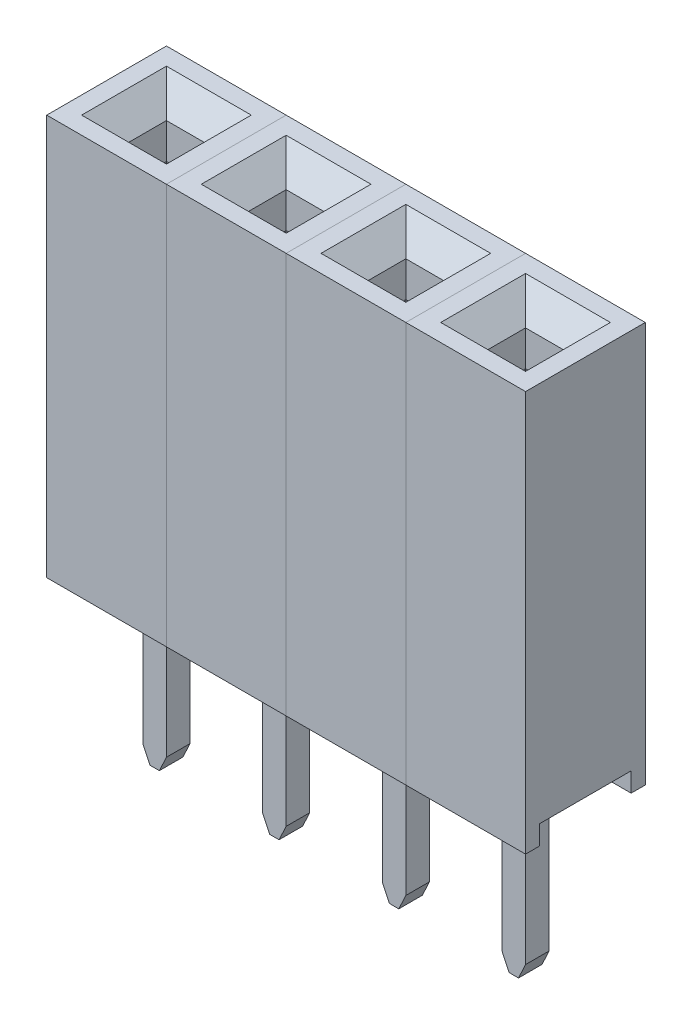
SolidWorks part; units mm, degrees
ref_plane "Front" through (0, 0, 0) normal (0, 0, 1) x (1, 0, 0)
ref_plane "Top" through (0, 0, 0) normal (0, 1, 0) x (1, 0, 0)
ref_plane "Right" through (0, 0, 0) normal (1, 0, 0) x (0, 0, -1)
sketch "Sketch1" plane through (0, 0, 0) normal (0, 0, 1) x (1, 0, 0)
  line L1 (1.27, -4.25) -> (-1.27, -4.25)
  line L2 (1.27, -4.25) -> (1.27, 4.25)
  line L3 (1.27, 4.25) -> (-1.27, 4.25)
  line L4 (-1.27, -4.25) -> (-1.27, 4.25)
  line L5 (1.27, -4.25) -> (-1.27, 4.25) construction
  line L6 (1.27, 4.25) -> (-1.27, -4.25) construction
  point P0 (0, 0)
  dimension "D1" = 2.54
  dimension "D2" = 8.5
extrude "Boss-Extrude1" add sketch "Sketch1" along normal mid plane 2.54
sketch "Sketch2" plane through (0, 0, 0) normal (1, 0, 0) x (0, 0, -1)
  line L0 (-0.97, -4.25) -> (0.97, -4.25)
  line L1 (-1.27, -4.25) -> (1.27, -4.25) construction
  line L2 (0.97, -4.25) -> (0.97, -3.8396)
  line L3 (0.97, -3.8396) -> (-0.97, -3.8396)
  line L4 (-0.97, -3.8396) -> (-0.97, -4.25)
  line L5 (1.27, -4.25) -> (1.27, 4.25) construction
  line L6 (-1.27, -4.25) -> (-1.27, 4.25) construction
  dimension "D1" = 0.3
  dimension "D2" = 0.3
extrude "Cut-Extrude1" cut sketch "Sketch2" against normal mid plane 100
sketch "Sketch4" plane through (0, 4.25, 0) normal (0, 1, 0) x (1, 0, 0)
  line L0 (-1.27, 0) -> (1.27, 0) construction
  line L1 (-1.27, -1.27) -> (-1.27, 1.27) construction
  line L2 (1.27, -1.27) -> (1.27, 1.27) construction
  line L4 (-0.875, 0.875) -> (0.875, 0.875)
  line L5 (-0.875, 0.875) -> (-0.875, -0.875)
  line L6 (-0.875, -0.875) -> (0.875, -0.875)
  line L7 (0.875, 0.875) -> (0.875, -0.875)
  line L8 (-0.875, 0.875) -> (0.875, -0.875) construction
  line L9 (-0.875, -0.875) -> (0.875, 0.875) construction
  line L10 (-0.4, 0.4) -> (0.4, 0.4)
  line L11 (-0.4, 0.4) -> (-0.4, -0.4)
  line L12 (-0.4, -0.4) -> (0.4, -0.4)
  line L13 (0.4, 0.4) -> (0.4, -0.4)
  line L14 (-0.4, 0.4) -> (0.4, -0.4) construction
  line L15 (-0.4, -0.4) -> (0.4, 0.4) construction
  point P6 (0, 0)
  point P11 (0, 0)
  point P16 (0, 0)
  dimension "D1" = 1.75
  dimension "D2" = 0.8
extrude "Cut-Extrude2" cut sketch "Sketch4" against normal blind 1.5 contours L13 L10 L11 L12 region at (0, 4.25, 0)
chamfer "Chamfer1" distance 0.5 angle 45 4 edges at (0, 4.25, -0.4) (-0.4, 4.25, 0) (0, 4.25, 0.4) (0.4, 4.25, 0)
sketch "Sketch5" plane through (0, 0, 0) normal (0, 1, 0) x (1, 0, 0)
  line L1 (-0.9, 0.9) -> (0.9, 0.9)
  line L2 (-0.9, 0.9) -> (-0.9, -0.9)
  line L3 (-0.9, -0.9) -> (0.9, -0.9)
  line L4 (0.9, 0.9) -> (0.9, -0.9)
extrude "Cut-Extrude3" cut sketch "Sketch5" against normal blind 3 and the other way blind 3
sketch "Sketch9" plane through (0, 0, 0) normal (0, 0, 1) x (1, 0, 0)
  line L0 (0, 1.6008) -> (0, -6.2684) construction
  line L1 (0.8528, -1.3416) -> (0.6022, -1.2609)
  line L2 (0.6022, -1.2609) -> (0.4133, 1.4919)
  line L3 (0.2803, 1.3393) -> (0.5075, -1.9717)
  line L4 (0.8528, -1.3416) -> (0.8528, -2.6933)
  line L5 (0.8528, -2.6933) -> (0.2807, -3.0533)
  line L6 (0.2807, -3.0533) -> (-0.2807, -3.0533)
  line L7 (-0.8528, -2.6933) -> (-0.2807, -3.0533)
  line L8 (-0.8528, -1.3416) -> (-0.8528, -2.6933)
  line L9 (-0.8528, -1.3416) -> (-0.6022, -1.2609)
  line L10 (-0.6022, -1.2609) -> (-0.4133, 1.4919)
  line L11 (-0.2803, 1.3393) -> (-0.5075, -1.9717)
  line L12 (-0.1, -7.6212) -> (0.1, -7.6212)
  line L13 (0.1, -7.6212) -> (0.25, -7.2995)
  line L14 (0.25, -7.2995) -> (0.25, -3.0533)
  line L15 (-0.1, -7.6212) -> (-0.25, -7.2995)
  line L16 (-0.25, -7.2995) -> (-0.25, -3.0533)
  line L19 (0, 0) -> (0, -10.2857) construction
  arc A0 (0.4133, 1.4919) -> (0.2803, 1.3393) centre (0.2705, 1.4821) ccw
  arc A1 (0.5075, -1.9717) -> (0, -2.3943) centre (0.101, -1.9996) cw
  arc A2 (-0.5075, -1.9717) -> (0, -2.3943) centre (-0.101, -1.9996) ccw
  arc A3 (-0.4133, 1.4919) -> (-0.2803, 1.3393) centre (-0.2705, 1.4821) cw
  point P16 (0, -3.0533)
  point P24 (-0.25, -4.3212)
  dimension "D1" = 115
  dimension "D2" = 115
  dimension "D3" = 0.25
  dimension "D4" = 0.2
  dimension "D5" = 0.25
  dimension "D6" = 3.3
extrude "Boss-Extrude4" add sketch "Sketch9" along normal mid plane 1.7 contours A1 L0 L6 L5 L4 L1 L2 A0 L3 | L0 A2 L11 A3 L10 L9 L8 L7 L6 region at (0.478, -1.4346, 0) region at (-0.478, -1.4346, 0)
extrude "Boss-Extrude5" add sketch "Sketch9<3>" along normal mid plane 0.5 contours L16 L15 L12 L13 L14 L6 region at (0, -5.2903, 0)
sketch "Sketch9<3>" plane through (0, 0, 0) normal (0, 0, 1) x (1, 0, 0) same geometry as "Sketch9"
pattern_linear "LPattern1" count 4 spacing 2.54 along (-1, 0, 0) of bodies 108
